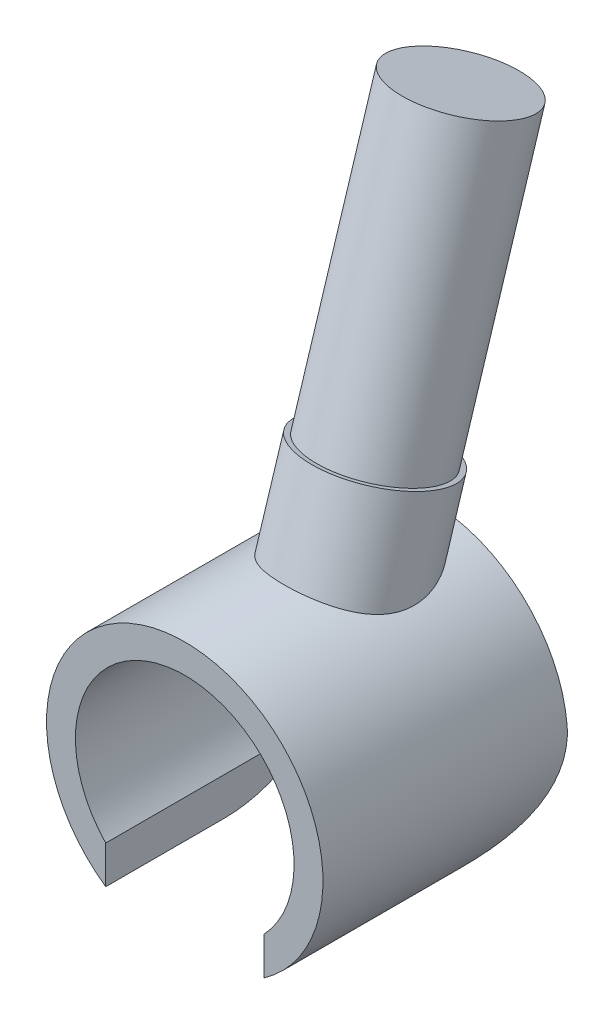
SolidWorks part; units mm, degrees
ref_plane "Front Plane" through (0, 0, 0) normal (0, 0, 1) x (1, 0, 0)
ref_plane "Top Plane" through (0, 0, 0) normal (0, 1, 0) x (1, 0, 0)
ref_plane "Right Plane" through (0, 0, 0) normal (1, 0, 0) x (0, 0, -1)
sketch "Sketch1" plane through (0, 0, 0) normal (0, 0, 1) x (1, 0, 0)
  line L0 (0, 0) -> (0, -2.44) construction
  line L1 (-1.395, -1.3337) -> (-1.395, -2.0019)
  line L2 (1.395, -1.3337) -> (1.395, -2.0019)
  arc A0 (1.395, -1.3337) -> (-1.395, -1.3337) centre (0, 0) ccw
  arc A1 (1.395, -2.0019) -> (-1.395, -2.0019) centre (0, 0) ccw
  dimension "D1" = 3.86
  dimension "D2" = 4.88
  dimension "D3" = 2.79
extrude "Boss-Extrude1" add sketch "Sketch1" along normal blind 4.32
sketch "Sketch2" plane through (0, 0, 0) normal (1, 0, 0) x (0, 0, -1)
  line L0 (0.5528, 8.54) -> (-2.7286, -2.0019) construction
  line L1 (-4.32, 2.44) -> (-4.32, -2.0019) construction
  line L2 (0.5528, 8.54) -> (-2.7286, 9.5614) construction
  line L3 (-4.32, -2.0019) -> (0, -2.0019) construction
  line L4 (0, -2.0019) -> (0, 2.44) construction
  line L5 (0, 0.2181) -> (0, -2.0019)
  line L6 (0, -2.0019) -> (-2.22, -2.0019)
  arc A0 (0, 0.2181) -> (-2.22, -2.0019) centre (-2.22, 0.2181) cw
  point P2 (-0.96, 3.68)
  dimension "D5" = 2.22
  dimension "D1" = 17.29
  dimension "D2" = 1.24
  dimension "D3" = 3.36
  dimension "D4" = 6.1
ref_plane "Plane2" through (0, 7.9425, -2.4723) normal (0, 0.9548, -0.2972) x (1, 0, 0)
sketch "Sketch4" plane through (0, 7.9425, -2.4723) normal (0, 0.9548, -0.2972) x (1, 0, 0)
  circle A0 centre (0, -2.0103) radius 1.08
  circle A1 centre (0, -2.0103) radius 1.17
  point P0 (0, -2.0103)
  dimension "D1" = 2.16
  dimension "D2" = 2.34
extrude "Boss-Extrude2" add sketch "Sketch4" against normal up to surface (6.7249 mm away) contours A0 region at (0, 8.54, -0.5528) up to face at (0, 0.2191, 2.16)
ref_plane "Plane3" through (0, 3.68, 0.96) normal (0, -0.9548, 0.2972) x (-1, 0, 0)
extrude "Boss-Extrude3" add sketch "Sketch4<3>" against normal up to surface (0.9345 mm away) from surface contours A1 A0 region at (-1.1369, 8.54, -0.5528) up to face at (-0.0982, 2.438, 0.2202) starting at plane "Plane3"
sketch "Sketch4<3>" plane through (0, 7.9425, -2.4723) normal (0, 0.9548, -0.2972) x (1, 0, 0) same geometry as "Sketch4"
extrude "Cut-Extrude1" cut sketch "Sketch2" against normal through all both and the other way through all contours L5 A0 L6 region at (0, -1.506, 0.4959)
